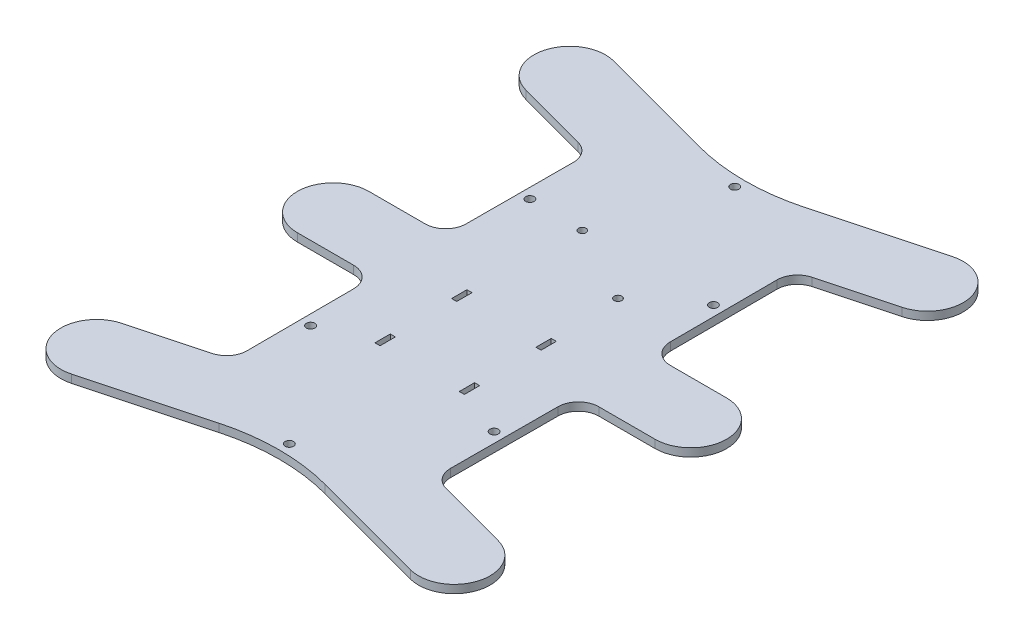
SolidWorks part; units mm, degrees
ref_plane "Front Plane" through (0, 0, 0) normal (0, 0, 1) x (1, 0, 0)
ref_plane "Top Plane" through (0, 0, 0) normal (0, 1, 0) x (1, 0, 0)
ref_plane "Right Plane" through (0, 0, 0) normal (1, 0, 0) x (0, 0, -1)
sketch "Sketch1" plane through (0, 0, 0) normal (0, 1, 0) x (1, 0, 0)
  line L0 (0, 32.1883) -> (0, -21.4181) construction
  line L1 (0, 0) -> (27.1703, 0) construction
  line L2 (-70, 14) -> (-40, 14)
  line L3 (-40, 14) -> (-39.8161, 70)
  line L4 (-39.8161, 70) -> (-73.6235, 79.0587)
  line L5 (-66.3765, 106.1046) -> (0, 88.3191)
  line L10 (-66.3765, 106.1046) -> (-73.6235, 79.0587) construction
  line L12 (-70, 14) -> (-70, -14) construction
  line L14 (-66.3765, -106.1046) -> (0, -88.3191)
  line L15 (-39.8161, -70) -> (-73.6235, -79.0587)
  line L16 (-40, -14) -> (-39.8161, -70)
  line L17 (-70, -14) -> (-40, -14)
  line L18 (66.3765, -106.1046) -> (0, -88.3191)
  line L19 (66.3765, 106.1046) -> (0, 88.3191)
  line L20 (70, 14) -> (70, -14) construction
  line L21 (66.3765, 106.1046) -> (73.6235, 79.0587) construction
  line L22 (70, -14) -> (40, -14)
  line L23 (40, -14) -> (39.8161, -70)
  line L24 (39.8161, -70) -> (73.6235, -79.0587)
  line L25 (39.8161, 70) -> (73.6235, 79.0587)
  line L26 (40, 14) -> (39.8161, 70)
  line L27 (70, 14) -> (40, 14)
  arc A0 (-70, 14) -> (-70, -14) centre (-70, 0) ccw
  arc A1 (-66.3765, 106.1046) -> (-73.6235, 79.0587) centre (-70, 92.5816) ccw
  arc A11 (-66.3765, -106.1046) -> (-73.6235, -79.0587) centre (-70, -92.5816) cw
  arc A18 (66.3765, -106.1046) -> (73.6235, -79.0587) centre (70, -92.5816) ccw
  arc A22 (66.3765, 106.1046) -> (73.6235, 79.0587) centre (70, 92.5816) cw
  arc A23 (70, 14) -> (70, -14) centre (70, 0) cw
  point P118 (-83.523, 96.2051)
  dimension "D2" = 14
  dimension "D3" = 70
  dimension "D1" = 75
  dimension "D5" = 30
  dimension "D6" = 35
  dimension "D7" = 56
extrude "Boss-Extrude1" add sketch "Sketch1" along normal blind 3.175
fillet "Fillet1" radius 80 2 edges at (0, 1.5875, -88.3191) (0, 1.5875, 88.3191)
fillet "Fillet2" radius 8 8 edges at (39.8161, 1.5875, 70) (40, 1.5875, 14) (40, 1.5875, -14) (39.8161, 1.5875, -70) (-39.8161, 1.5875, -70) (-40, 1.5875, -14) (-40, 1.5875, 14) (-39.8161, 1.5875, 70)
sketch "Sketch2" plane through (0, 3.175, 0) normal (0, 1, 0) x (1, 0, 0)
  line L0 (0, 91.1411) -> (0, -91.1411) construction
  line L1 (-84, 0) -> (84, 0) construction
  line L2 (39.9738, 21.9737) -> (39.8363, 63.8405) construction
  line L3 (-39.8363, 63.8405) -> (-39.9738, 21.9737) construction
  line L4 (-39.9051, 42.9071) -> (39.9051, 42.9071) construction
  arc A0 (-20.7055, 93.8671) -> (20.7055, 93.8671) centre (0, 171.1411) ccw construction
  arc A1 (20.7055, -93.8671) -> (-20.7055, -93.8671) centre (0, -171.1411) ccw construction
  arc A2 (-70, 14) -> (-70, -14) centre (-70, 0) ccw construction
  arc A3 (70, -14) -> (70, 14) centre (70, 0) ccw construction
  circle A4 centre (0, 87.1411) radius 1.65
  circle A5 centre (-35.905, 42.9071) radius 1.65
  circle A6 centre (35.905, 42.9071) radius 1.65
  circle A7 centre (35.905, -42.9071) radius 1.65
  circle A8 centre (0, -87.1411) radius 1.65
  circle A9 centre (-35.905, -42.9071) radius 1.65
  point P18 (39.9051, 42.9071)
  point P21 (-39.9051, 42.9071)
  dimension "D4" = 3.3
  dimension "D1" = 4
  dimension "D2" = 4
  dimension "D3" = 4
extrude "Cut-Extrude1" cut sketch "Sketch2" against normal blind 10
sketch "Sketch3" plane through (0, 3.175, 0) normal (0, 1, 0) x (1, 0, 0)
  arc A0 (13.5, 26.5) -> (16.5, 26.5) centre (15, 26.5) ccw construction
  arc A1 (16.5, 26.5) -> (13.5, 26.5) centre (15, 26.5) ccw construction
  arc A2 (-16.5, 42.5) -> (-13.5, 42.5) centre (-15, 42.5) ccw construction
  arc A3 (-13.5, 42.5) -> (-16.5, 42.5) centre (-15, 42.5) ccw construction
  arc A4 (13.5, 26.5) -> (16.5, 26.5) centre (15, 26.5) ccw
  arc A5 (16.5, 26.5) -> (13.5, 26.5) centre (15, 26.5) ccw
  arc A6 (-16.5, 42.5) -> (-13.5, 42.5) centre (-15, 42.5) ccw
  arc A7 (-13.5, 42.5) -> (-16.5, 42.5) centre (-15, 42.5) ccw
extrude "Cut-Extrude2" cut sketch "Sketch3" against normal blind 10
sketch "Sketch4" plane through (0, 3.175, 0) normal (0, 1, 0) x (1, 0, 0)
  line L0 (0, -91.1411) -> (0, 91.1411) construction
  line L1 (-15.5, -30.1411) -> (-15.5, -36.1411)
  line L2 (17.5, -0.1411) -> (15.5, -0.1411)
  line L3 (17.5, -0.1411) -> (17.5, -6.1411)
  line L4 (17.5, -6.1411) -> (15.5, -6.1411)
  line L5 (15.5, -0.1411) -> (15.5, -6.1411)
  line L6 (17.5, -30.1411) -> (15.5, -30.1411)
  line L7 (17.5, -30.1411) -> (17.5, -36.1411)
  line L8 (17.5, -36.1411) -> (15.5, -36.1411)
  line L9 (15.5, -30.1411) -> (15.5, -36.1411)
  line L10 (-17.5, -36.1411) -> (-15.5, -36.1411)
  line L11 (-17.5, -30.1411) -> (-17.5, -36.1411)
  line L12 (-17.5, -30.1411) -> (-15.5, -30.1411)
  line L13 (-15.5, -0.1411) -> (-15.5, -6.1411)
  line L14 (-17.5, -6.1411) -> (-15.5, -6.1411)
  line L15 (-17.5, -0.1411) -> (-17.5, -6.1411)
  line L16 (-17.5, -0.1411) -> (-15.5, -0.1411)
  arc A0 (20.7055, -93.8671) -> (-20.7055, -93.8671) centre (0, -171.1411) ccw construction
  arc A1 (-20.7055, 93.8671) -> (20.7055, 93.8671) centre (0, 171.1411) ccw construction
  dimension "D1" = 2
  dimension "D2" = 6
  dimension "D3" = 24
  dimension "D4" = 55
  dimension "D5" = 15.5
extrude "Cut-Extrude3" cut sketch "Sketch4" against normal blind 10
equation "\"D2@Sketch2\"=\"D1@Sketch2\""
equation "\"D3@Sketch2\"=\"D1@Sketch2\""
